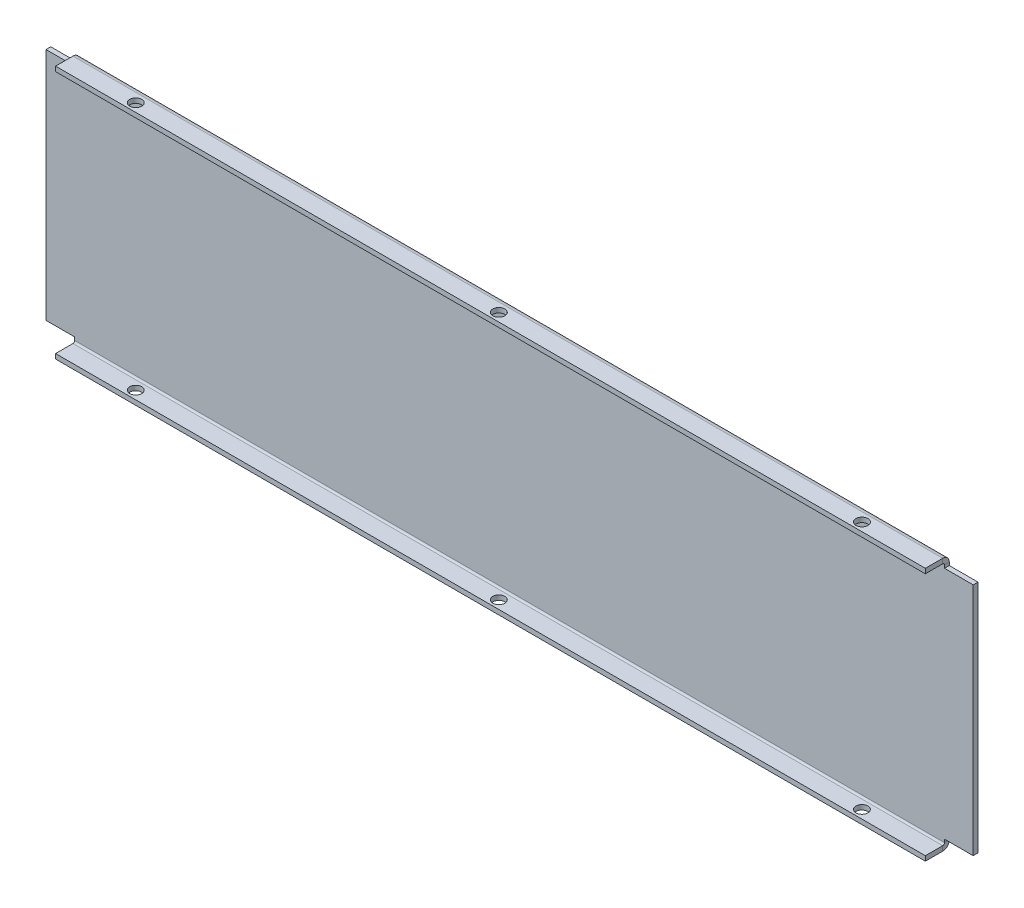
SolidWorks part; units mm, degrees
note: The reader was unsure of these and kept them because the rebuilt part matched: flange length of "Edge-Flange1", "Edge-Flange2".
material "ASTM A36 Steel"
ref_plane "Front Plane" through (0, 0, 0) normal (0, 0, 1) x (1, 0, 0)
ref_plane "Top Plane" through (0, 0, 0) normal (0, 1, 0) x (1, 0, 0)
ref_plane "Right Plane" through (0, 0, 0) normal (1, 0, 0) x (0, 0, -1)
sketch "Sketch1" plane through (0, 0, 0) normal (0, 0, 1) x (1, 0, 0)
  line L1 (-193.7, 53) -> (193.7, 53)
  line L2 (-193.7, 53) -> (-193.7, -53)
  line L3 (-193.7, -53) -> (193.7, -53)
  line L4 (193.7, 53) -> (193.7, -53)
  line L5 (-193.7, 53) -> (193.7, -53) construction
  line L6 (-193.7, -53) -> (193.7, 53) construction
  point P0 (0, 0)
  dimension "D1" = 387.4
  dimension "D2" = 106
base flange "Base-Flange1" sketch "Sketch1" thickness 2 reverse thickness direction no parameters "D1"=0.7366
edge flange "Edge-Flange1" sketch "Sketch10" flange angle 90 flange length 10 flange position material inside bend radius 0.7366 thickness 2 relief rectangular parameters "D6"=10
sketch "Sketch10" plane through (0, 53, 0) normal (0, 1, 0) x (-1, 0, 0)
  line L0 (-193.7, 0) -> (193.7, 0) construction
  line L1 (-193.7, 0) -> (193.7, 0)
  line L2 (-193.7, 0) -> (-193.7, 8)
  line L3 (-193.7, 8) -> (193.7, 8)
  line L4 (193.7, 8) -> (193.7, 0)
bend "EdgeBend1" bend radius 0.7366 bend angle 90 parameters "D5"=1
edge flange "Edge-Flange2" sketch "Sketch13" flange angle 90 flange length 10 flange position material inside bend radius 0.7366 thickness 2 relief rectangular parameters "D6"=10
sketch "Sketch13" plane through (0, -53, 0) normal (0, -1, 0) x (1, 0, 0)
  line L0 (-193.7, 0) -> (193.7, 0) construction
  line L1 (-193.7, 0) -> (193.7, 0)
  line L2 (-193.7, 0) -> (-193.7, 8)
  line L3 (-193.7, 8) -> (193.7, 8)
  line L4 (193.7, 8) -> (193.7, 0)
bend "EdgeBend2" bend radius 0.7366 bend angle 90 parameters "D5"=2
sketch "Sketch14" plane through (0, 53, 0) normal (0, 1, 0) x (1, 0, 0)
  line L0 (-193.7, -0.7366) -> (-193.7, -8) construction
  line L1 (-255.606, 24.4058) -> (-181.7, 24.4058)
  line L2 (-255.606, 24.4058) -> (-255.606, -19.6258)
  line L3 (-255.606, -19.6258) -> (-181.7, -19.6258)
  line L4 (-181.7, 24.4058) -> (-181.7, -19.6258)
  dimension "D1" = 12
extrude "Cut-Extrude1" cut sketch "Sketch14" against normal blind 4 normal cut yes
mirror "Mirror1" about plane through (0, 0, 0) normal (0, 1, 0) of "Cut-Extrude1"
mirror "Mirror2" about plane through (0, 0, 0) normal (1, 0, 0) of "Mirror1", "Cut-Extrude1"
sketch "Sketch15" plane through (0, 53, 0) normal (0, 1, 0) x (1, 0, 0)
  circle A0 centre (151.7, -4.5) radius 2.5
  circle A1 centre (0, -4.5) radius 2.5
  circle A2 centre (-151.7, -4.5) radius 2.5
extrude "Cut-Extrude2" cut sketch "Sketch15" against normal through all both and the other way through all normal cut yes
sketch "Bend-Lines1" [suppressed] plane through (0, 0, 0) normal (0, 1, 0) x (1, 0, 0)
sketch "Bounding-Box1" [suppressed] plane through (0, 0, 0) normal (0, 1, 0) x (1, 0, 0)
sheet metal parameters "Sheet-Metal1" thickness 2 parameters "D1"=0.7366
flat pattern "Flat-Pattern1" [suppressed]
sketch "Bend-Lines2" plane through (0, 0, 0) normal (0, 1, 0) x (1, 0, 0)
sketch3d "Bounding-Box2" [suppressed]
  line L0 (171.2, -37.5, 0) -> (-171.2, -37.5, 0) construction
  line L1 (171.2, 37.5, 0) -> (-171.2, 37.5, 0) construction
  line L2 (171.2, -37.5, 0) -> (171.2, 37.5, 0) construction
  line L3 (-171.2, -37.5, 0) -> (-171.2, 37.5, 0) construction
sheet metal parameters "Sheet-Metal2" thickness 2 parameters "D1"=0.7366
flat pattern "Flat-Pattern1"
sketch "Bend-Lines2" plane through (0, 0, 0) normal (0, 0, 1) x (1, 0, 0)
  line L0 (171.2, 36.1273) -> (-171.2, 36.1273) construction
  line L1 (171.2, 36.1273) -> (-171.2, 36.1273) construction
sketch3d "Bounding-Box2" [suppressed]
  line L0 (-171.2, -37.5, 0) -> (171.2, -37.5, 0) construction
  line L1 (-171.2, 44.7546, 0) -> (171.2, 44.7546, 0) construction
  line L2 (-171.2, -37.5, 0) -> (-171.2, 44.7546, 0) construction
  line L3 (171.2, -37.5, 0) -> (171.2, 44.7546, 0) construction
bend of the flat pattern "Flatten-<EdgeBend1>1"
sheet metal parameters "Sheet-Metal3" thickness 2 parameters "D1"=0.7366
flat pattern "Flat-Pattern1"
sketch "Bend-Lines2" plane through (0, 0, 0) normal (0, 0, 1) x (1, 0, 0)
  line L0 (193.7, 51.6273) -> (-193.7, 51.6273) construction
  line L1 (193.7, 51.6273) -> (-193.7, 51.6273) construction
  line L2 (-193.7, -51.6273) -> (193.7, -51.6273) construction
  line L3 (-193.7, -51.6273) -> (193.7, -51.6273) construction
sketch3d "Bounding-Box2" [suppressed]
  line L0 (-193.7, -60.2546, 0) -> (193.7, -60.2546, 0) construction
  line L1 (-193.7, 60.2546, 0) -> (193.7, 60.2546, 0) construction
  line L2 (-193.7, -60.2546, 0) -> (-193.7, 60.2546, 0) construction
  line L3 (193.7, -60.2546, 0) -> (193.7, 60.2546, 0) construction
bend of the flat pattern "Flatten-<EdgeBend1>1"
bend of the flat pattern "Flatten-<EdgeBend2>1"
sheet metal parameters "Sheet-Metal4" thickness 2 parameters "D1"=0.7366
flat pattern "Flat-Pattern1"
sketch "Bend-Lines2" plane through (0, 0, 0) normal (0, 0, 1) x (1, 0, 0)
  line L0 (193.7, 51.6273) -> (-181.7, 51.6273) construction
  line L1 (193.7, 51.6273) -> (-181.7, 51.6273) construction
  line L2 (-193.7, -51.6273) -> (193.7, -51.6273) construction
  line L3 (-193.7, -51.6273) -> (193.7, -51.6273) construction
sketch3d "Bounding-Box2" [suppressed]
  line L0 (-193.7, -60.2546, 0) -> (193.7, -60.2546, 0) construction
  line L1 (-193.7, 60.2546, 0) -> (193.7, 60.2546, 0) construction
  line L2 (-193.7, -60.2546, 0) -> (-193.7, 60.2546, 0) construction
  line L3 (193.7, -60.2546, 0) -> (193.7, 60.2546, 0) construction
bend of the flat pattern "Flatten-<EdgeBend1>1"
bend of the flat pattern "Flatten-<EdgeBend2>1"
sheet metal parameters "Sheet-Metal5" thickness 2 parameters "D1"=0.7366
flat pattern "Flat-Pattern1"
sketch "Bend-Lines2" plane through (0, 0, 0) normal (0, 0, 1) x (1, 0, 0)
  line L0 (193.7, 51.6273) -> (-181.7, 51.6273) construction
  line L1 (193.7, 51.6273) -> (-181.7, 51.6273) construction
  line L2 (-181.7, -51.6273) -> (193.7, -51.6273) construction
  line L3 (-181.7, -51.6273) -> (193.7, -51.6273) construction
sketch3d "Bounding-Box2" [suppressed]
  line L0 (-193.7, -60.2546, 0) -> (193.7, -60.2546, 0) construction
  line L1 (-193.7, 60.2546, 0) -> (193.7, 60.2546, 0) construction
  line L2 (-193.7, -60.2546, 0) -> (-193.7, 60.2546, 0) construction
  line L3 (193.7, -60.2546, 0) -> (193.7, 60.2546, 0) construction
bend of the flat pattern "Flatten-<EdgeBend1>1"
bend of the flat pattern "Flatten-<EdgeBend2>1"
sheet metal parameters "Sheet-Metal6" thickness 2 parameters "D1"=0.7366
flat pattern "Flat-Pattern1"
sketch "Bend-Lines2" plane through (0, 0, 0) normal (0, 0, 1) x (1, 0, 0)
  line L0 (181.7, 51.6273) -> (-181.7, 51.6273) construction
  line L1 (181.7, 51.6273) -> (-181.7, 51.6273) construction
  line L2 (-181.7, -51.6273) -> (181.7, -51.6273) construction
  line L3 (-181.7, -51.6273) -> (181.7, -51.6273) construction
sketch3d "Bounding-Box2" [suppressed]
  line L0 (-193.7, -60.2546, 0) -> (193.7, -60.2546, 0) construction
  line L1 (-193.7, 60.2546, 0) -> (193.7, 60.2546, 0) construction
  line L2 (-193.7, -60.2546, 0) -> (-193.7, 60.2546, 0) construction
  line L3 (193.7, -60.2546, 0) -> (193.7, 60.2546, 0) construction
bend of the flat pattern "Flatten-<EdgeBend1>1"
bend of the flat pattern "Flatten-<EdgeBend2>1"
sheet metal parameters "Sheet-Metal8" thickness 2 parameters "D1"=0.7366
flat pattern "Flat-Pattern1"
sketch "Bend-Lines2" plane through (0, 0, 0) normal (0, 0, 1) x (1, 0, 0)
  line L0 (181.7, 51.6273) -> (-181.7, 51.6273) construction
  line L1 (181.7, 51.6273) -> (-181.7, 51.6273) construction
  line L2 (-181.7, -51.6273) -> (181.7, -51.6273) construction
  line L3 (-181.7, -51.6273) -> (181.7, -51.6273) construction
sketch3d "Bounding-Box2" [suppressed]
  line L0 (-193.7, -60.2546, 0) -> (193.7, -60.2546, 0) construction
  line L1 (-193.7, 60.2546, 0) -> (193.7, 60.2546, 0) construction
  line L2 (-193.7, -60.2546, 0) -> (-193.7, 60.2546, 0) construction
  line L3 (193.7, -60.2546, 0) -> (193.7, 60.2546, 0) construction
bend of the flat pattern "Flatten-<EdgeBend1>1"
bend of the flat pattern "Flatten-<EdgeBend2>1"
